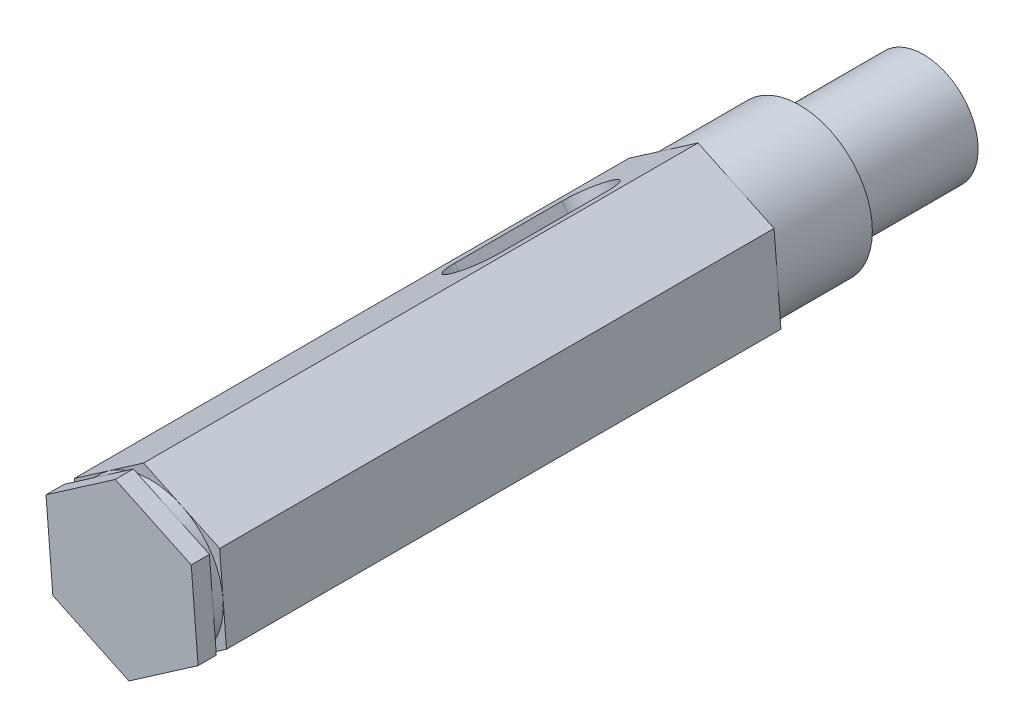
SolidWorks part; units mm, degrees
ref_plane "Front Plane" through (0, 0, 0) normal (0, 0, 1) x (1, 0, 0)
ref_plane "Top Plane" through (0, 0, 0) normal (0, 1, 0) x (1, 0, 0)
ref_plane "Right Plane" through (0, 0, 0) normal (1, 0, 0) x (0, 0, -1)
sketch "Sketch1" plane through (0, 0, 0) normal (0, 0, 1) x (1, 0, 0)
  line L1 (6.0296, 4.1722) -> (-0.5985, 7.3079)
  line L2 (-0.5985, 7.3079) -> (-6.6281, 3.1356)
  line L3 (-6.6281, 3.1356) -> (-6.0296, -4.1722)
  line L4 (-6.0296, -4.1722) -> (0.5985, -7.3079)
  line L5 (0.5985, -7.3079) -> (6.6281, -3.1356)
  line L6 (6.6281, -3.1356) -> (6.0296, 4.1722)
  circle A0 centre (0, 0) radius 6.35 construction
  circle A1 centre (0, 0) radius 2.7305
  dimension "D2" = 5.461
  dimension "D1" = 12.7
extrude "Boss-Extrude1" add sketch "Sketch1" along normal blind 20.9042
sketch "Sketch2" plane through (0, 0, 20.9042) normal (0, 0, 1) x (1, 0, 0)
  line L1 (-6.6281, 3.1356) -> (-6.0296, -4.1722)
  line L2 (-6.0296, -4.1722) -> (0.5985, -7.3079)
  line L3 (0.5985, -7.3079) -> (6.6281, -3.1356)
  line L4 (6.6281, -3.1356) -> (6.0296, 4.1722)
  line L5 (6.0296, 4.1722) -> (-0.5985, 7.3079)
  line L6 (-0.5985, 7.3079) -> (-6.6281, 3.1356)
  circle A0 centre (0, 0) radius 6.35 construction
extrude "Boss-Extrude2" add sketch "Sketch2" along normal blind 29.8958
sketch "Sketch3" plane through (0, 0, 0) normal (0, 0, -1) x (-1, 0, 0)
  circle A0 centre (0, 0) radius 6.3411
  circle A1 centre (0, 0) radius 2.7305
  dimension "D1" = 12.6822
  dimension "D2" = 5.461
extrude "Boss-Extrude3" add sketch "Sketch3" along normal blind 19.05
sketch "Sketch4" plane through (-3.6133, 5.2218, 0) normal (-0.569, 0.8223, 0) x (0.8223, 0.569, 0)
  line L0 (0, -16.2306) -> (0, -6.858) construction
  line L1 (-2.3876, -16.2306) -> (-2.3876, -6.858)
  line L2 (2.3876, -16.2306) -> (2.3876, -6.858)
  line L4 (3.6662, 0) -> (-3.6662, 0) construction
  line L5 (3.6662, -50.8) -> (-3.6662, -50.8) construction
  arc A0 (-2.3876, -16.2306) -> (2.3876, -16.2306) centre (0, -16.2306) ccw
  arc A1 (2.3876, -6.858) -> (-2.3876, -6.858) centre (0, -6.858) ccw
  point P3 (0, -11.5443)
  dimension "D1" = 2.3876
  dimension "D2" = 34.5694
  dimension "D3" = 6.858
extrude "Cut-Extrude1" cut sketch "Sketch4" against normal up to surface (12.7 mm away) up to face at (3.6133, -5.2218, 25.4)
ref_plane "Plane1" through (0, 0, 49.2125) normal (0, 0, 1) x (1, 0, 0)
sketch "Sketch5" plane through (0, 0, 49.2125) normal (0, 0, 1) x (1, 0, 0)
  circle A0 centre (0, 0) radius 7.62
  circle A1 centre (0, 0) radius 6.35
  dimension "D1" = 15.24
  dimension "D2" = 12.7
extrude "Cut-Extrude4" cut sketch "Sketch5" against normal blind 0.889
sketch "Sketch6" plane through (0, 0, -19.05) normal (0, 0, -1) x (-1, 0, 0)
  circle A0 centre (0, 0) radius 6.35
  circle A1 centre (0, 0) radius 4.7625
  dimension "D1" = 9.525
  dimension "D2" = 12.7
extrude "Cut-Extrude5" cut sketch "Sketch6" against normal blind 10.795
